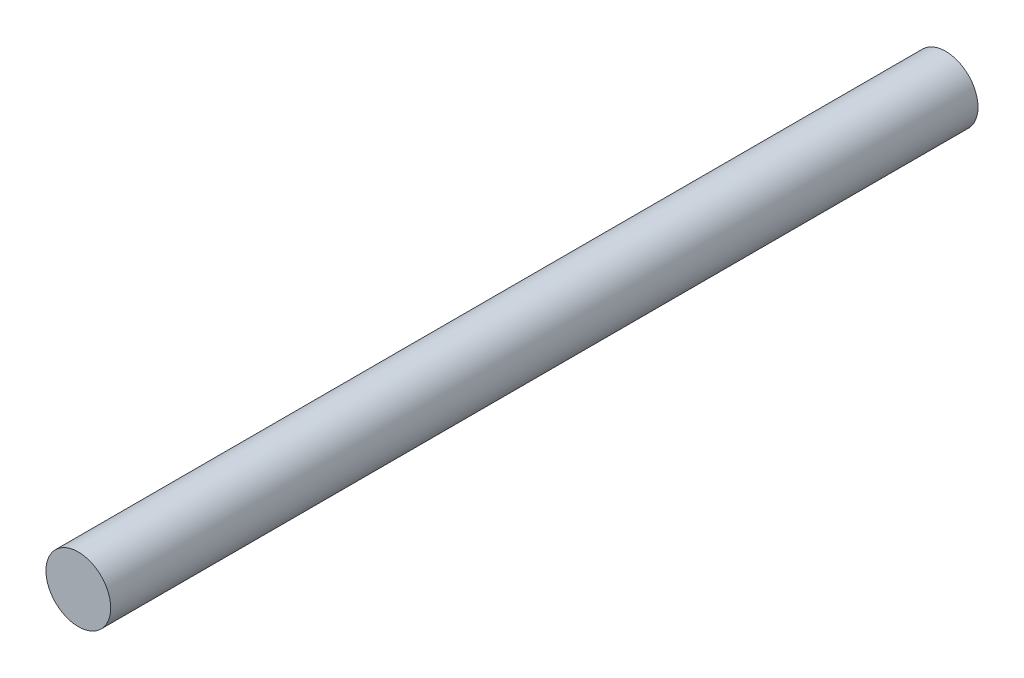
SolidWorks part; units mm, degrees
material "Magnetorquers"
ref_plane "Piano frontale" through (0, 0, 0) normal (0, 0, 1) x (1, 0, 0)
ref_plane "Piano superiore" through (0, 0, 0) normal (0, 1, 0) x (1, 0, 0)
ref_plane "Piano destro" through (0, 0, 0) normal (1, 0, 0) x (0, 0, -1)
sketch "Schizzo1" plane through (0, 0, 0) normal (0, 0, 1) x (1, 0, 0)
  circle A0 centre (0, 0) radius 28
  dimension "D1" = 56
extrude "Estrusione-Estrusione1" add sketch "Schizzo1" along normal blind 375 and the other way blind 375
